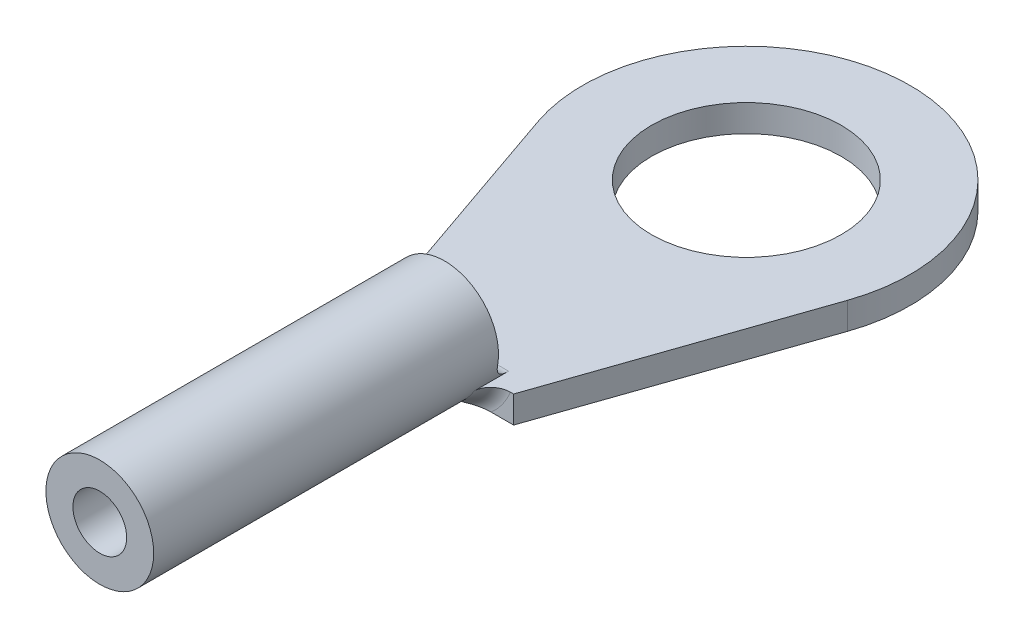
SolidWorks part; units mm, degrees
ref_plane "Front Plane" through (0, 0, 0) normal (0, 0, 1) x (1, 0, 0)
ref_plane "Top Plane" through (0, 0, 0) normal (0, 1, 0) x (1, 0, 0)
ref_plane "Right Plane" through (0, 0, 0) normal (1, 0, 0) x (0, 0, -1)
sketch "Sketch1" plane through (0, 0, 0) normal (0, 1, 0) x (1, 0, 0)
  line L0 (2.2805, -0.7887) -> (1.016, -4.445)
  line L1 (1.016, -4.445) -> (-1.016, -4.445)
  line L2 (-1.016, -4.445) -> (-2.2805, -0.7887)
  line L3 (0, 3.396) -> (0, -4.445) construction
  line L4 (0, -2.1683) -> (0, 2.1683) construction
  line L5 (-2.6543, 0) -> (2.6543, 0) construction
  circle A0 centre (0, 0) radius 1.397
  arc A1 (2.2805, -0.7887) -> (-2.2805, -0.7887) centre (0, 0) ccw
  point P9 (0, 0)
  point P12 (2.413, 0)
  point P13 (-2.413, 0)
  point P16 (2.4123, -0.0561)
  point P17 (2.3179, -0.6708)
  dimension "D1" = 2.794
  dimension "D2" = 2.413
  dimension "D3" = 4.445
  dimension "D4" = 2.032
extrude "Boss-Extrude1" add sketch "Sketch1" along normal blind 0.3969
sketch "Sketch3" plane through (0, 0, 4.445) normal (0, 0, 1) x (1, 0, 0)
  line L0 (0, -0.8731) -> (0, 0.8731) construction
  circle A0 centre (0, 0.7929) radius 0.7937
  circle A1 centre (0, 0.7929) radius 0.396
  dimension "D1" = 1.5875
extrude "Boss-Extrude2" add sketch "Sketch3" along normal blind 5.08
fillet "Fillet1" radius 0.254 2 edges
fillet "Fillet2" radius 0.254 2 edges at (0.3439, 0.3969, 4.445) (-0.3439, 0.3969, 4.445)
